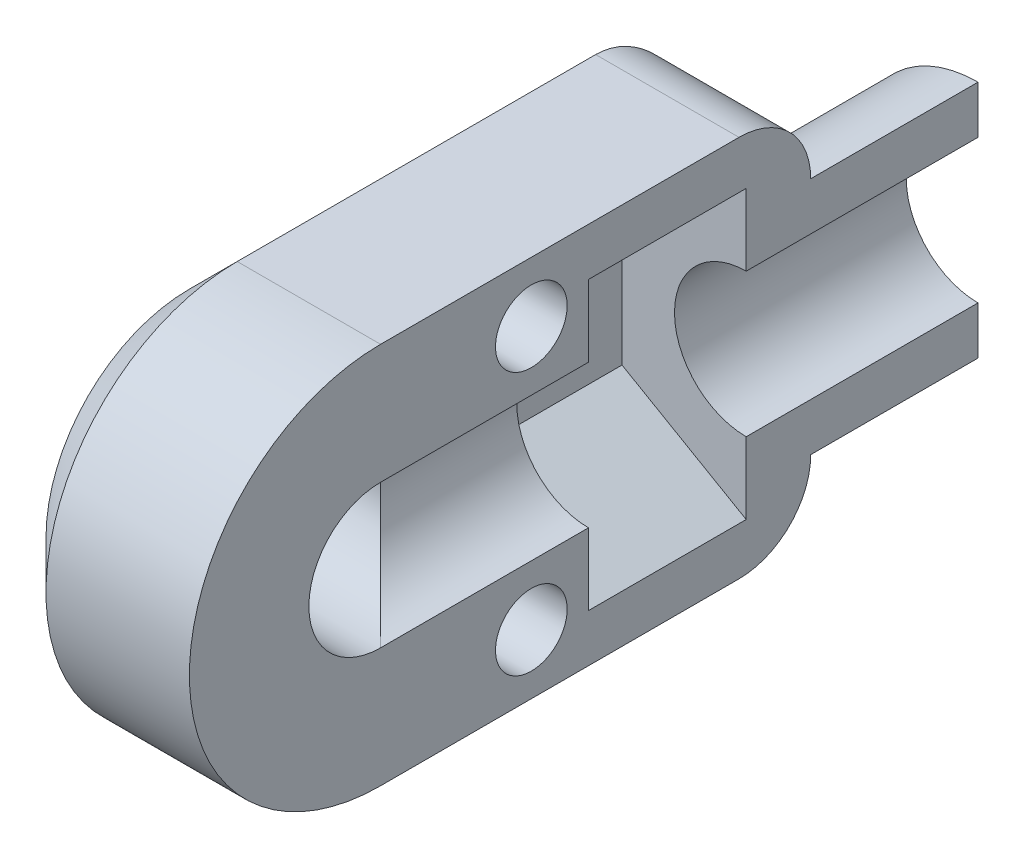
SolidWorks part; units mm, degrees
material "PLA"
ref_plane "Front Plane" through (0, 0, 0) normal (0, 0, 1) x (1, 0, 0)
ref_plane "Top Plane" through (0, 0, 0) normal (0, 1, 0) x (1, 0, 0)
ref_plane "Right Plane" through (0, 0, 0) normal (1, 0, 0) x (0, 0, -1)
sketch "Sketch1" plane through (0, 0, 0) normal (1, 0, 0) x (0, -1, 0)
  line L1 (-8, 0) -> (8, 0)
  line L2 (-8, 0) -> (-8, 25)
  line L3 (-8, 25) -> (8, 25)
  line L4 (8, 0) -> (8, 25)
  circle A0 centre (0, 0) radius 3
  circle A1 centre (0, 0) radius 8
  dimension "D1" = 6
  dimension "D2" = 16
  dimension "D3" = 25
extrude "Boss-Extrude1" add sketch "Sketch1" along normal blind 16 contours A1 L4 L3 L2 | L1 A1 A0 | L1 A1 A0 region at (0, 0, -3.7426) region at (0, 0, 3.7426) region at (0, 0, -15.5564)
chamfer "Chamfer2" distance 2 angle 45 6 edges at (0, 0, 8) (16, 8, -12.5) (0, 8, -12.5) (0, -8, -12.5) (16, -8, -12.5) (16, 0, 8)
sketch "Esquisse1" plane through (0, 0, -25) normal (0, 0, -1) x (-1, 0, 0)
  line L0 (-8, 8) -> (-8, -8) construction
  circle A0 centre (-8, 0) radius 3
  dimension "D1" = 6
extrude "Enlèv. mat.-Extru.1" cut sketch "Esquisse1" against normal up to surface (22 mm away) up to face at (16, 0, -3)
sketch "Esquisse2" plane through (0, 8, 0) normal (0, 1, 0) x (1, 0, 0)
  line L1 (8, 25) -> (17.7516, 25)
  line L2 (8, 25) -> (8, -9.2824)
  line L3 (8, -9.2824) -> (17.7516, -9.2824)
  line L4 (17.7516, 25) -> (17.7516, -9.2824)
extrude "Enlèv. mat.-Extru.2" cut sketch "Esquisse2" against normal blind 56
ref_plane "Plan1" through (0, 0, -12) normal (0, 0, 1) x (1, 0, 0)
sketch "Esquisse4" plane through (0, 0, -12) normal (0, 0, 1) x (1, 0, 0)
  line L0 (14, 8) -> (2, -8) construction
  line L1 (8, 0) -> (8, 11.1862) construction
  line L2 (13.1962, -3) -> (13.1962, 3)
  line L3 (13.1962, 3) -> (8, 6)
  line L4 (8, 6) -> (2.8038, 3)
  line L5 (2.8038, 3) -> (2.8038, -3)
  line L6 (2.8038, -3) -> (8, -6)
  line L7 (8, -6) -> (13.1962, -3)
  circle A1 centre (8, 0) radius 5.1962 construction
  point P12 (8, 0)
  dimension "D2" = 12
extrude "Enlèv. mat.-Extru.3" cut sketch "Esquisse4" against normal blind 3.3 and the other way blind 3.3
sketch "Esquisse8" plane through (8, 0, 0) normal (1, 0, 0) x (0, 0, -1)
  line L0 (8.7, 3) -> (0, 3) construction
  line L2 (-8, 0) -> (34.3103, 0) construction
  circle A0 centre (6.3089, 5.5) radius 1.5
  circle A1 centre (6.3089, -5.5) radius 1.5
  dimension "D1" = 3
  dimension "D2" = 2.5
extrude "Enlèv. mat.-Extru.4" cut sketch "Esquisse8" against normal blind 10.3
sketch "Esquisse9" plane through (0, 0, 0) normal (-1, 0, 0) x (0, 0, 1)
  line L0 (-25, 0) -> (14.7447, 0) construction
  circle A0 centre (-6.3089, 5.5) radius 2
  circle A1 centre (-6.3089, -5.5) radius 2
  point P0 (-6.3089, 5.5)
  dimension "D1" = 4
extrude "Enlèv. mat.-Extru.5" cut sketch "Esquisse9" against normal blind 2
sketch "Esquisse10" plane through (0, 0, -25) normal (0, 0, -1) x (-1, 0, 0)
  line L0 (-8, 5) -> (-8, -5.0415)
  arc A0 (-8, -5) -> (-8, 5) centre (-8, 0) ccw
  arc A1 (-8, -3) -> (-8, 3) centre (-8, 0) ccw construction
  line M2 (-8, -3) -> (-8, -8)
  line M3 (-8, -8) -> (-2, -8)
  line M4 (-2, -8) -> (0, -6)
  line M5 (0, -6) -> (0, 6)
  line M6 (0, 6) -> (-2, 8)
  line M7 (-2, 8) -> (-8, 8)
  line M8 (-8, 8) -> (-8, 3)
  dimension "D1" = 5
extrude "Enlèv. mat.-Extru.6" cut sketch "Esquisse10" against normal blind 7 contours A0 L0 M2 M3 M4 M5 M6 M7 M8 region at (7.8211, 6.5, -25)
fillet "Congé1" radius 3 5 edges at (5, -8, -18) (1, -7, -18) (0, 0, -18) (1, 7, -18) (5, 8, -18)
